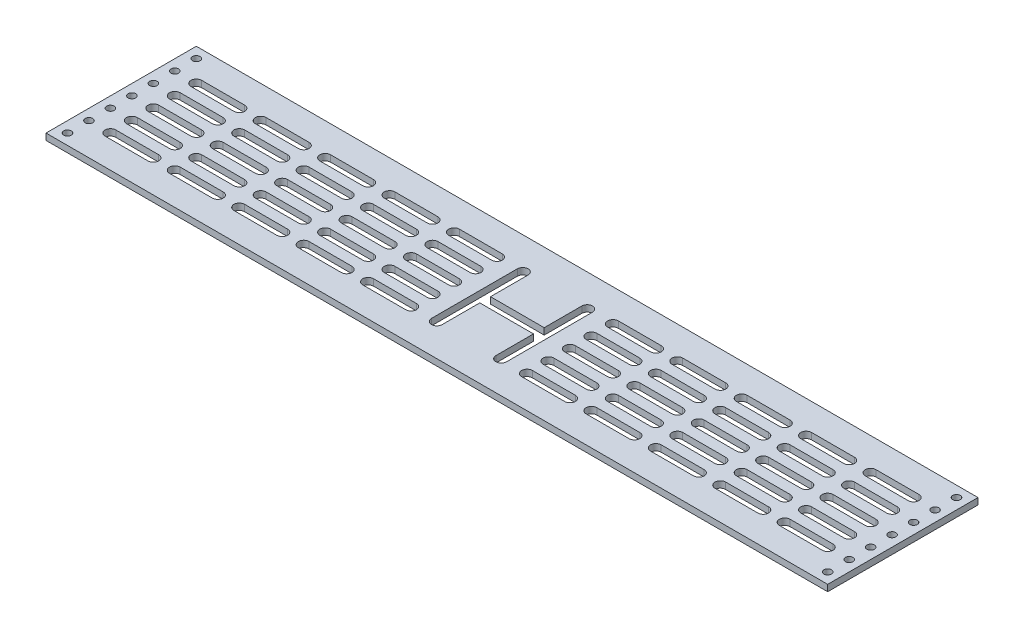
SolidWorks part; units mm, degrees
material "A-玻璃纤维"
ref_plane "前视基准面" through (0, 0, 0) normal (0, 0, 1) x (1, 0, 0)
ref_plane "上视基准面" through (0, 0, 0) normal (0, 1, 0) x (1, 0, 0)
ref_plane "右视基准面" through (0, 0, 0) normal (1, 0, 0) x (0, 0, -1)
other "Configuration Table"
sketch "草图1" plane through (0, 0, 0) normal (0, 1, 0) x (1, 0, 0)
  line L0 (0, 0) -> (-182, 0)
  line L1 (0, 0) -> (182, 0)
  line L2 (182, 0) -> (182, -80)
  line L3 (182, -80) -> (-182, -80)
  line L4 (-182, -80) -> (-182, 0)
extrude "凸台-拉伸1" add sketch "草图1" along normal blind 3
sketch "草图2" plane through (0, 3, 0) normal (0, 1, 0) x (1, 0, 0)
  line L0 (-182, -80) -> (-177, -80)
  line L1 (-182, -80) -> (182, -80) construction
  line L2 (-177, -80) -> (-177, 0)
  line L3 (182, 0) -> (-182, 0) construction
  line L4 (-177, -80) -> (-177, -75)
  line L5 (0, 0) -> (0, -80)
  circle A0 centre (-177, -75) radius 1.75
  circle A1 centre (-177, -65) radius 1.75
  circle A2 centre (-177, -55) radius 1.75
  circle A3 centre (-177, -45) radius 1.75
  circle A4 centre (-177, -35) radius 1.75
  circle A5 centre (-177, -25) radius 1.75
  circle A6 centre (-177, -15) radius 1.75
  circle A7 centre (-177, -5) radius 1.75
  circle A8 centre (177, -5) radius 1.75
  circle A9 centre (177, -15) radius 1.75
  circle A10 centre (177, -25) radius 1.75
  circle A11 centre (177, -35) radius 1.75
  circle A12 centre (177, -45) radius 1.75
  circle A13 centre (177, -55) radius 1.75
  circle A14 centre (177, -65) radius 1.75
  circle A15 centre (177, -75) radius 1.75
  dimension "D1" = 8
  dimension "D2" = 3.5
  dimension "D3" = 5
extrude "切除-拉伸1" cut sketch "草图2" against normal through all contours L4 A0 L2 | L2 A0 L4 | L2 A1 | L2 A1 | L2 A2 | L2 A2 | L2 A3 | L2 A3 | L2 A4 | L2 A4 | L2 A5 | L2 A5 | L2 A6 | L2 A6 | L2 A7 | L2 A7 | A8 | A9 | A10 | A11 | A12 | A13 | A14 | A15 region at (-177.7427, 3, 75) region at (-177.7427, 3, 5) region at (-176.2573, 3, 5) region at (-177.7427, 3, 15) region at (-176.2573, 3, 15) region at (-177.7427, 3, 25) region at (-176.2573, 3, 25) region at (-177.7427, 3, 35) region at (-176.2573, 3, 35) region at (-177.7427, 3, 45) region at (-176.2573, 3, 45) region at (-177.7427, 3, 55) region at (-176.2573, 3, 55) region at (-177.7427, 3, 65) region at (-176.2573, 3, 65) region at (-176.2573, 3, 75) region at (177, 3, 5) region at (177, 3, 15) region at (177, 3, 25) region at (177, 3, 35) region at (177, 3, 45) region at (177, 3, 55) region at (177, 3, 65) region at (177, 3, 75)
sketch "草图3" plane through (0, 3, 0) normal (0, 1, 0) x (1, 0, 0)
  line L0 (0, -80) -> (0, -45)
  line L1 (182, 0) -> (-182, 0) construction
  line L2 (-182, -80) -> (182, -80) construction
  line L3 (0, -45) -> (-15, -45)
  line L4 (0, -45) -> (15, -45)
  line L5 (15, -45) -> (15, -25)
  line L6 (15, -45) -> (15, -65)
  line L7 (-15, -45) -> (-15, -25)
  line L8 (-15, -45) -> (-15, -65)
  line L9 (-15, -45) -> (15, -45) construction
  line L10 (-12.5, -42.5) -> (12.5, -42.5)
  line L11 (-12.5, -47.5) -> (12.5, -47.5)
  line L12 (-15, -25) -> (-15, -65) construction
  line L13 (-12.5, -25) -> (-12.5, -42.5)
  line L14 (-17.5, -25) -> (-17.5, -65)
  line L15 (15, -25) -> (15, -65) construction
  line L16 (17.5, -25) -> (17.5, -65)
  line L17 (12.5, -25) -> (12.5, -42.5)
  line L18 (12.5, -47.5) -> (12.5, -65)
  line L19 (-12.5, -47.5) -> (-12.5, -65)
  line L20 (-182, -80) -> (0, -80)
  line L21 (-91, -80) -> (-91, 0)
  line L22 (-177, -65) -> (-91, -65)
  line L23 (-177, -65) -> (-167, -65)
  line L24 (-167, -65) -> (-147, -65)
  line L25 (-147, -65) -> (-137, -65)
  line L26 (-137, -65) -> (-117, -65)
  line L27 (-117, -65) -> (-107, -65)
  line L28 (-107, -65) -> (-87, -65)
  line L29 (-87, -65) -> (-77, -65)
  line L30 (-77, -65) -> (-57, -65)
  line L31 (-167, -65) -> (-147, -65) construction
  line L32 (-167, -62.5) -> (-147, -62.5)
  line L33 (-167, -67.5) -> (-147, -67.5)
  line L34 (-137, -65) -> (-117, -65) construction
  line L35 (-137, -62.5) -> (-117, -62.5)
  line L36 (-137, -67.5) -> (-117, -67.5)
  line L37 (-107, -65) -> (-87, -65) construction
  line L38 (-107, -62.5) -> (-87, -62.5)
  line L39 (-107, -67.5) -> (-87, -67.5)
  line L40 (-77, -65) -> (-57, -65) construction
  line L41 (-77, -62.5) -> (-57, -62.5)
  line L42 (-77, -67.5) -> (-57, -67.5)
  line L43 (-167, -57.5) -> (-147, -57.5)
  line L44 (-167, -52.5) -> (-147, -52.5)
  line L45 (-137, -57.5) -> (-117, -57.5)
  line L46 (-137, -52.5) -> (-117, -52.5)
  line L47 (-107, -57.5) -> (-87, -57.5)
  line L48 (-107, -52.5) -> (-87, -52.5)
  line L49 (-77, -57.5) -> (-57, -57.5)
  line L50 (-77, -52.5) -> (-57, -52.5)
  line L51 (-167, -55) -> (-147, -55) construction
  line L52 (-137, -55) -> (-117, -55) construction
  line L53 (-107, -55) -> (-87, -55) construction
  line L54 (-77, -55) -> (-57, -55) construction
  line L55 (-167, -47.5) -> (-147, -47.5)
  line L56 (-167, -42.5) -> (-147, -42.5)
  line L57 (-137, -47.5) -> (-117, -47.5)
  line L58 (-137, -42.5) -> (-117, -42.5)
  line L59 (-107, -47.5) -> (-87, -47.5)
  line L60 (-107, -42.5) -> (-87, -42.5)
  line L61 (-77, -47.5) -> (-57, -47.5)
  line L62 (-77, -42.5) -> (-57, -42.5)
  line L63 (-167, -45) -> (-147, -45) construction
  line L64 (-137, -45) -> (-117, -45) construction
  line L65 (-107, -45) -> (-87, -45) construction
  line L66 (-77, -45) -> (-57, -45) construction
  line L67 (-167, -37.5) -> (-147, -37.5)
  line L68 (-167, -32.5) -> (-147, -32.5)
  line L69 (-137, -37.5) -> (-117, -37.5)
  line L70 (-137, -32.5) -> (-117, -32.5)
  line L71 (-107, -37.5) -> (-87, -37.5)
  line L72 (-107, -32.5) -> (-87, -32.5)
  line L73 (-77, -37.5) -> (-57, -37.5)
  line L74 (-77, -32.5) -> (-57, -32.5)
  line L75 (-167, -35) -> (-147, -35) construction
  line L76 (-137, -35) -> (-117, -35) construction
  line L77 (-107, -35) -> (-87, -35) construction
  line L78 (-77, -35) -> (-57, -35) construction
  line L87 (-157, -45) -> (-157, -35)
  line L88 (-157, -35) -> (-157, -25)
  line L89 (-157, -25) -> (-167, -25)
  line L90 (-157, -25) -> (-147, -25)
  line L99 (-147, -25) -> (-137, -25)
  line L100 (-137, -25) -> (-117, -25)
  line L101 (-117, -25) -> (-107, -25)
  line L102 (-107, -25) -> (-87, -25)
  line L109 (-87, -25) -> (-77, -25)
  line L112 (-77, -25) -> (-57, -25)
  line L115 (-57, -25) -> (-47, -25)
  line L118 (-47, -25) -> (-27, -25)
  line L121 (-167, -25) -> (-147, -25) construction
  line L124 (-167, -22.5) -> (-147, -22.5)
  line L175 (-167, -27.5) -> (-147, -27.5)
  line L178 (-137, -25) -> (-117, -25) construction
  line L181 (-57, -65) -> (-47, -65)
  line L182 (-47, -65) -> (-27, -65)
  line L183 (-47, -65) -> (-27, -65) construction
  line L184 (-47, -62.5) -> (-27, -62.5)
  line L185 (-47, -67.5) -> (-27, -67.5)
  line L186 (-47, -57.5) -> (-27, -57.5)
  line L187 (-47, -52.5) -> (-27, -52.5)
  line L188 (-47, -55) -> (-27, -55) construction
  line L189 (-47, -47.5) -> (-27, -47.5)
  line L190 (-47, -42.5) -> (-27, -42.5)
  line L191 (-47, -45) -> (-27, -45) construction
  line L192 (-47, -37.5) -> (-27, -37.5)
  line L193 (-47, -32.5) -> (-27, -32.5)
  line L194 (-47, -35) -> (-27, -35) construction
  line L197 (-137, -22.5) -> (-117, -22.5)
  line L200 (-137, -27.5) -> (-117, -27.5)
  line L202 (-107, -25) -> (-87, -25) construction
  line L205 (-107, -22.5) -> (-87, -22.5)
  line L220 (-167, -22.5) -> (-147, -22.5) [skipped]
  line L221 (-167, -27.5) -> (-147, -27.5) [skipped]
  line L222 (-137, -22.5) -> (-117, -22.5) [skipped]
  line L223 (-137, -27.5) -> (-117, -27.5) [skipped]
  line L224 (-107, -22.5) -> (-87, -22.5) [skipped]
  line L225 (-107, -27.5) -> (-87, -27.5) [skipped]
  line L226 (-77, -22.5) -> (-57, -22.5) [skipped]
  line L227 (-77, -27.5) -> (-57, -27.5) [skipped]
  line L228 (-167, -12.5) -> (-147, -12.5) [skipped]
  line L229 (-167, -17.5) -> (-147, -17.5) [skipped]
  line L230 (-137, -12.5) -> (-117, -12.5) [skipped]
  line L231 (-137, -17.5) -> (-117, -17.5) [skipped]
  line L232 (-107, -12.5) -> (-87, -12.5) [skipped]
  line L233 (-107, -17.5) -> (-87, -17.5) [skipped]
  line L234 (-77, -12.5) -> (-57, -12.5) [skipped]
  line L235 (-77, -17.5) -> (-57, -17.5) [skipped]
  line L236 (-47, -22.5) -> (-27, -22.5) [skipped]
  line L237 (-47, -27.5) -> (-27, -27.5) [skipped]
  line L238 (-47, -12.5) -> (-27, -12.5) [skipped]
  line L239 (-47, -17.5) -> (-27, -17.5) [skipped]
  line L240 (-107, -27.5) -> (-87, -27.5)
  line L241 (-77, -25) -> (-57, -25) construction
  line L242 (-77, -22.5) -> (-57, -22.5)
  line L243 (-77, -27.5) -> (-57, -27.5)
  line L244 (-47, -25) -> (-27, -25) construction
  line L245 (-47, -22.5) -> (-27, -22.5)
  line L246 (-47, -27.5) -> (-27, -27.5)
  arc A2 (-12.5, -25) -> (-17.5, -25) centre (-15, -25) ccw
  arc A3 (-17.5, -65) -> (-12.5, -65) centre (-15, -65) ccw
  arc A4 (17.5, -25) -> (12.5, -25) centre (15, -25) ccw
  arc A5 (12.5, -65) -> (17.5, -65) centre (15, -65) ccw
  arc A6 (-167, -62.5) -> (-167, -67.5) centre (-167, -65) ccw
  arc A7 (-147, -67.5) -> (-147, -62.5) centre (-147, -65) ccw
  arc A8 (-137, -62.5) -> (-137, -67.5) centre (-137, -65) ccw
  arc A9 (-117, -67.5) -> (-117, -62.5) centre (-117, -65) ccw
  arc A10 (-107, -62.5) -> (-107, -67.5) centre (-107, -65) ccw
  arc A11 (-87, -67.5) -> (-87, -62.5) centre (-87, -65) ccw
  arc A12 (-77, -62.5) -> (-77, -67.5) centre (-77, -65) ccw
  arc A13 (-57, -67.5) -> (-57, -62.5) centre (-57, -65) ccw
  arc A14 (-167, -52.5) -> (-167, -57.5) centre (-167, -55) ccw
  arc A15 (-147, -57.5) -> (-147, -52.5) centre (-147, -55) ccw
  arc A16 (-137, -52.5) -> (-137, -57.5) centre (-137, -55) ccw
  arc A17 (-117, -57.5) -> (-117, -52.5) centre (-117, -55) ccw
  arc A18 (-107, -52.5) -> (-107, -57.5) centre (-107, -55) ccw
  arc A19 (-87, -57.5) -> (-87, -52.5) centre (-87, -55) ccw
  arc A20 (-77, -52.5) -> (-77, -57.5) centre (-77, -55) ccw
  arc A21 (-57, -57.5) -> (-57, -52.5) centre (-57, -55) ccw
  arc A22 (-167, -42.5) -> (-167, -47.5) centre (-167, -45) ccw
  arc A23 (-147, -47.5) -> (-147, -42.5) centre (-147, -45) ccw
  arc A24 (-137, -42.5) -> (-137, -47.5) centre (-137, -45) ccw
  arc A25 (-117, -47.5) -> (-117, -42.5) centre (-117, -45) ccw
  arc A26 (-107, -42.5) -> (-107, -47.5) centre (-107, -45) ccw
  arc A27 (-87, -47.5) -> (-87, -42.5) centre (-87, -45) ccw
  arc A28 (-77, -42.5) -> (-77, -47.5) centre (-77, -45) ccw
  arc A29 (-57, -47.5) -> (-57, -42.5) centre (-57, -45) ccw
  arc A30 (-167, -32.5) -> (-167, -37.5) centre (-167, -35) ccw
  arc A31 (-147, -37.5) -> (-147, -32.5) centre (-147, -35) ccw
  arc A32 (-137, -32.5) -> (-137, -37.5) centre (-137, -35) ccw
  arc A33 (-117, -37.5) -> (-117, -32.5) centre (-117, -35) ccw
  arc A34 (-107, -32.5) -> (-107, -37.5) centre (-107, -35) ccw
  arc A35 (-87, -37.5) -> (-87, -32.5) centre (-87, -35) ccw
  arc A36 (-77, -32.5) -> (-77, -37.5) centre (-77, -35) ccw
  arc A37 (-57, -37.5) -> (-57, -32.5) centre (-57, -35) ccw
  arc A102 (-47, -62.5) -> (-47, -67.5) centre (-47, -65) ccw
  arc A103 (-27, -67.5) -> (-27, -62.5) centre (-27, -65) ccw
  arc A104 (-47, -52.5) -> (-47, -57.5) centre (-47, -55) ccw
  arc A105 (-27, -57.5) -> (-27, -52.5) centre (-27, -55) ccw
  arc A106 (-47, -42.5) -> (-47, -47.5) centre (-47, -45) ccw
  arc A107 (-27, -47.5) -> (-27, -42.5) centre (-27, -45) ccw
  arc A108 (-47, -32.5) -> (-47, -37.5) centre (-47, -35) ccw
  arc A109 (-27, -37.5) -> (-27, -32.5) centre (-27, -35) ccw
  arc A126 (-167, -22.5) -> (-167, -27.5) centre (-167, -25) ccw [skipped]
  arc A127 (-147, -27.5) -> (-147, -22.5) centre (-147, -25) ccw [skipped]
  arc A128 (-137, -22.5) -> (-137, -27.5) centre (-137, -25) ccw [skipped]
  arc A129 (-117, -27.5) -> (-117, -22.5) centre (-117, -25) ccw [skipped]
  arc A130 (-107, -22.5) -> (-107, -27.5) centre (-107, -25) ccw [skipped]
  arc A131 (-87, -27.5) -> (-87, -22.5) centre (-87, -25) ccw [skipped]
  arc A132 (-77, -22.5) -> (-77, -27.5) centre (-77, -25) ccw [skipped]
  arc A133 (-57, -27.5) -> (-57, -22.5) centre (-57, -25) ccw [skipped]
  arc A134 (-167, -12.5) -> (-167, -17.5) centre (-167, -15) ccw [skipped]
  arc A135 (-147, -17.5) -> (-147, -12.5) centre (-147, -15) ccw [skipped]
  arc A136 (-137, -12.5) -> (-137, -17.5) centre (-137, -15) ccw [skipped]
  arc A137 (-117, -17.5) -> (-117, -12.5) centre (-117, -15) ccw [skipped]
  arc A138 (-107, -12.5) -> (-107, -17.5) centre (-107, -15) ccw [skipped]
  arc A139 (-87, -17.5) -> (-87, -12.5) centre (-87, -15) ccw [skipped]
  arc A140 (-77, -12.5) -> (-77, -17.5) centre (-77, -15) ccw [skipped]
  arc A141 (-57, -17.5) -> (-57, -12.5) centre (-57, -15) ccw [skipped]
  arc A142 (-47, -22.5) -> (-47, -27.5) centre (-47, -25) ccw [skipped]
  arc A143 (-27, -27.5) -> (-27, -22.5) centre (-27, -25) ccw [skipped]
  arc A144 (-47, -12.5) -> (-47, -17.5) centre (-47, -15) ccw [skipped]
  arc A145 (-27, -17.5) -> (-27, -12.5) centre (-27, -15) ccw [skipped]
  arc A146 (-167, -22.5) -> (-167, -27.5) centre (-167, -25) ccw
  arc A147 (-147, -27.5) -> (-147, -22.5) centre (-147, -25) ccw
  arc A148 (-137, -22.5) -> (-137, -27.5) centre (-137, -25) ccw
  arc A149 (-117, -27.5) -> (-117, -22.5) centre (-117, -25) ccw
  arc A150 (-107, -22.5) -> (-107, -27.5) centre (-107, -25) ccw
  arc A151 (-87, -27.5) -> (-87, -22.5) centre (-87, -25) ccw
  arc A152 (-77, -22.5) -> (-77, -27.5) centre (-77, -25) ccw
  arc A153 (-57, -27.5) -> (-57, -22.5) centre (-57, -25) ccw
  arc A154 (-47, -22.5) -> (-47, -27.5) centre (-47, -25) ccw
  arc A155 (-27, -27.5) -> (-27, -22.5) centre (-27, -25) ccw
  point P8 (0, -40)
  point P18 (-15, -40)
  point P23 (15, -40)
  point P43 (-157, -65)
  point P48 (-127, -65)
  point P53 (-97, -65)
  point P58 (-67, -65)
  point P73 (-157, -55)
  point P78 (-127, -55)
  point P83 (-97, -55)
  point P88 (-67, -55)
  point P101 (-157, -45)
  point P106 (-127, -45)
  point P111 (-97, -45)
  point P116 (-67, -45)
  point P129 (-157, -35)
  point P134 (-127, -35)
  point P139 (-97, -35)
  point P144 (-67, -35)
  point P160 (-157, -25)
  point P166 (-127, -25)
  point P171 (-97, -25)
  point P176 (-67, -25)
  point P181 (-37, -25)
  point P374 (-37, -65)
  point P383 (-37, -55)
  point P390 (-37, -45)
  point P397 (-37, -35)
  dimension "D3" = 6
  dimension "D4" = 6
  dimension "D1" = 15
  dimension "D2" = 35
  dimension "D5" = 20
  dimension "D6" = 15
  dimension "D7" = 20
  dimension "D8" = 10
extrude "切除-拉伸4" cut sketch "草图3" against normal through all contours L33 A7 L22 L23 A6 | L22 A7 L32 A6 L23 | L43 A15 L44 A14 | L55 A23 L56 A22 | L67 A31 L68 A30 | L69 A33 L70 A32 | L57 A25 L58 A24 | L45 A17 L46 A16 | L36 A9 L22 A8 | L22 A9 L35 A8 | L22 A10 L39 L21 | L48 A18 L47 L21 | L60 A26 L59 L21 | L72 A34 L71 L21 | L71 A35 L72 L21 | L59 A27 L60 L21 | L47 A19 L48 L21 | L39 A11 L29 L28 L21 | L38 A10 L22 L21 | L29 A11 L38 L21 L28 | L42 A13 L181 L30 L29 A12 | L181 A13 L41 A12 L29 L30 | L185 A103 L184 A102 | L186 A105 L187 A104 | L189 A107 L190 A106 | L192 A109 L193 A108 | L73 A37 L74 A36 | L61 A29 L62 A28 | L49 A21 L50 A20 | L18 A5 L16 A4 L17 L10 L13 A2 L14 A3 L19 L11 | L68 A30 L67 L87 L88 | L175 A147 L99 L90 L88 | L200 A149 L101 L100 L99 A148 | L101 A149 L197 A148 L99 L100 | L205 A150 L101 L102 L21 | L101 A150 L240 L21 L102 | L243 A153 L115 L112 L109 A152 | L115 A153 L242 A152 L109 L112 | L99 A147 L124 A146 L175 L88 L90 | L246 A155 L245 A154 | L190 A107 L189 A106 | A151 L205 A150 L240 region at (-6.25, 3, 46.9299) region at (-157, 3, 66.219) region at (-157, 3, 63.781) region at (-127, 3, 66.219) region at (-127, 3, 63.781) region at (-152, 3, 42.755) region at (-151.0052, 3, 35) region at (-162.9948, 3, 35) region at (-151.0052, 3, 26.219) region at (-158.9983, 3, 24.5937) region at (-127, 3, 26.219) region at (-127, 3, 23.781) region at (-48.5875, 3, 23.4125) region at (-67, 3, 23.781) region at (-67, 3, 26.219) region at (-99.9904, 3, 26.2293) region at (-99.9904, 3, 35) region at (-87.9921, 3, 35) region at (-99.9904, 3, 45) region at (-87.9921, 3, 45) region at (-99.9904, 3, 55) region at (-87.9921, 3, 55) region at (-48.5875, 3, 63.4125) region at (-67, 3, 63.781) region at (-67, 3, 66.219) region at (-99.9904, 3, 66.2293) region at (-87.9921, 3, 66.1878) region at (-99.9904, 3, 63.7707) region at (-87.9921, 3, 63.8122) region at (-99.9904, 3, 23.7707) region at (-157, 3, 55) region at (-127, 3, 55) region at (-67, 3, 55) region at (-127, 3, 45) region at (-67, 3, 45) region at (-127, 3, 35) region at (-67, 3, 35) region at (-37, 3, 55) region at (-37, 3, 45) region at (-37, 3, 35)
sketch "草图4" plane through (0, 0, 0) normal (0, -1, 0) x (1, 0, 0)
  line L0 (177, 15) -> (177, 10)
  line L1 (177, 10) -> (187.2333, 10)
  line L2 (182, 0) -> (182.1166, 10)
  line L3 (182.1166, 10) -> (-182, 10)
  line L4 (-182, 0) -> (-182, 80) construction
  line L5 (-182, 10) -> (-182, 0)
  line L6 (-182, 0) -> (182, 0)
extrude "切除-拉伸3" cut sketch "草图4" against normal blind 10 contours L5 L6 L2 L1 L3 region at (0.0292, 0, 5.0003)
mirror "镜向1" about plane through (0, 0, 0) normal (1, 0, 0) of "切除-拉伸4"
